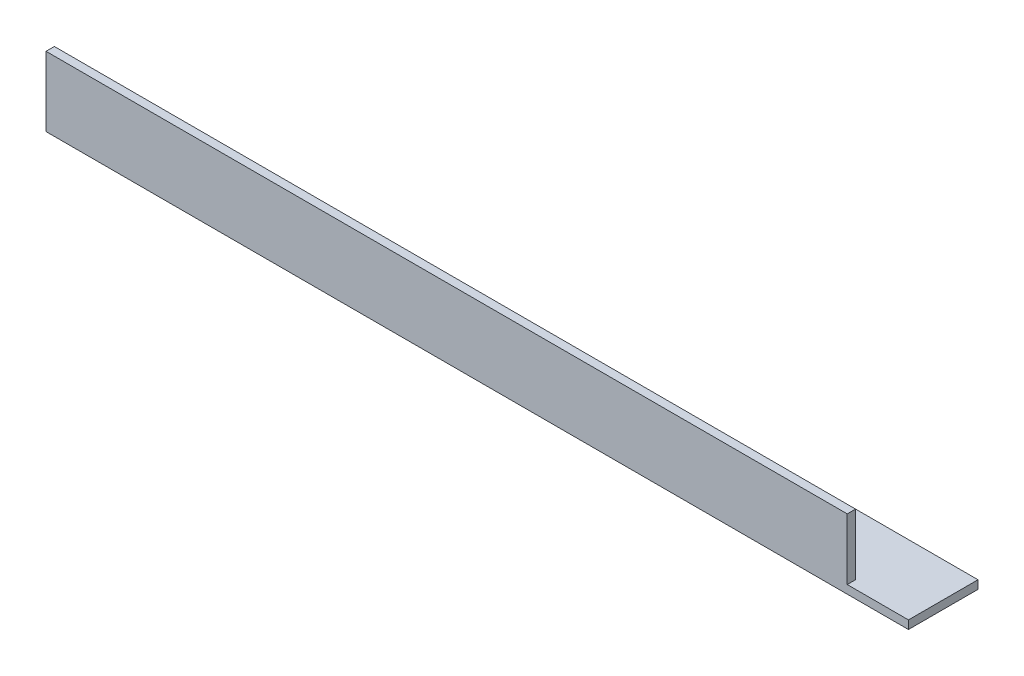
SolidWorks part; units mm, degrees
ref_plane "Спереди" through (0, 0, 0) normal (0, 0, 1) x (1, 0, 0)
ref_plane "Сверху" through (0, 0, 0) normal (0, 1, 0) x (1, 0, 0)
ref_plane "Справа" through (0, 0, 0) normal (1, 0, 0) x (0, 0, -1)
sketch "Эскиз1" plane through (0, 0, 0) normal (1, 0, 0) x (0, 0, -1)
  line L0 (0, 0) -> (25, 0)
  line L1 (0, 0) -> (0, 25)
extrude "Вытянуть-Тонкостенный1" add sketch "Эскиз1" along normal blind 310 thin thin type one direction wall 3
sketch "Эскиз2" plane through (0, 0, 0) normal (0, 0, 1) x (1, 0, 0)
  line L1 (310, 25) -> (288, 25)
  line L2 (310, 25) -> (310, 3)
  line L3 (310, 3) -> (288, 3)
  line L4 (288, 25) -> (288, 3)
extrude "Вырез-Вытянуть1" cut sketch "Эскиз2" against normal through all
